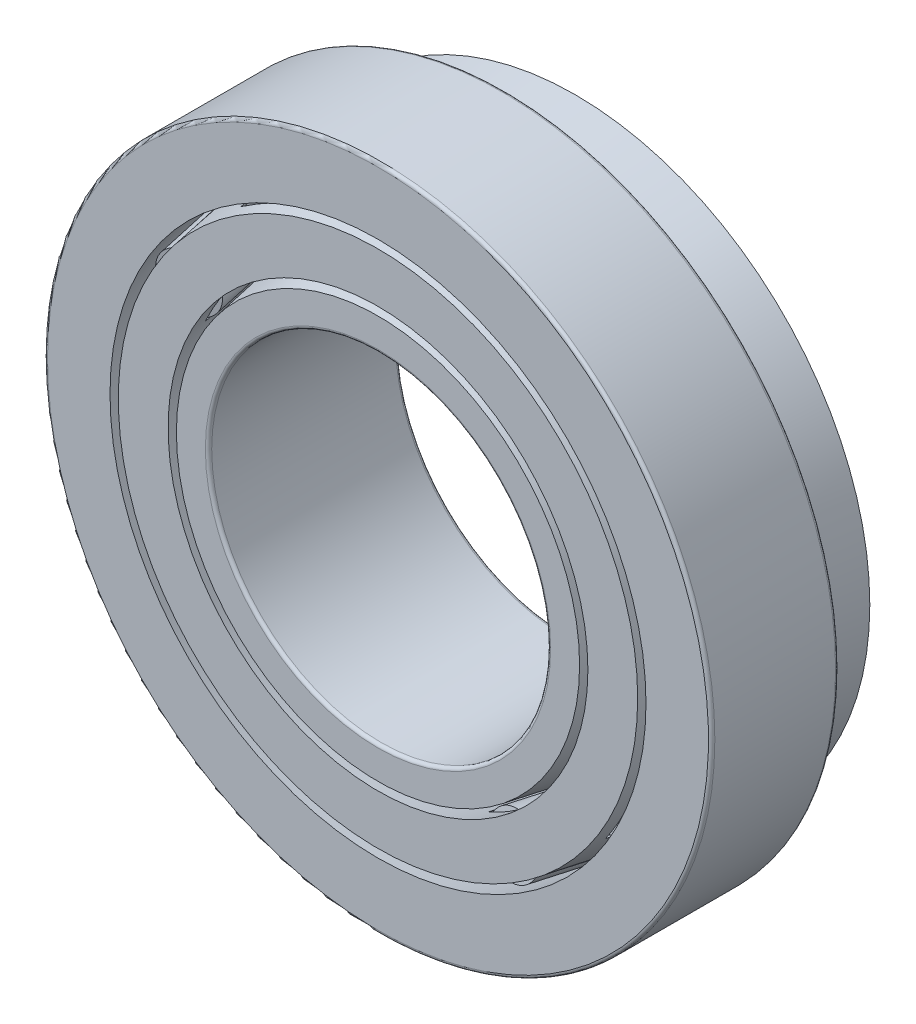
SolidWorks part; units mm, degrees
material "AISI 304"
ref_plane "Front Plane" through (0, 0, 0) normal (0, 0, 1) x (1, 0, 0)
ref_plane "Top Plane" through (0, 0, 0) normal (0, 1, 0) x (1, 0, 0)
ref_plane "Right Plane" through (0, 0, 0) normal (1, 0, 0) x (0, 0, -1)
sketch "Sketch1" plane through (0, 0, 0) normal (1, 0, 0) x (0, 0, -1)
  line L0 (-7.1298, 0) -> (7.1298, 0) construction
  line L1 (0, 0) -> (0, 25.0025) construction
  line L2 (-7.1298, 12.7) -> (7.1298, 12.7) construction
  line L3 (7.1298, 12.7) -> (7.1298, 17.621) construction
  line L4 (7.1298, 17.621) -> (-7.1298, 15.1067) construction
  line L5 (-7.1298, 15.1067) -> (-7.1298, 12.7) construction
  line L7 (-7.1298, 25.0025) -> (2.3952, 25.0025)
  line L8 (2.3952, 25.0025) -> (2.3952, 21.761)
  line L9 (2.3952, 21.761) -> (-7.1298, 20.0815)
  line L10 (-7.1298, 20.0815) -> (-7.1298, 25.0025)
  line L11 (-7.1298, 20.0815) -> (-6.279, 15.2567) construction
  line L12 (7.549, 22.6698) -> (8.3998, 17.8449) construction
  line L14 (-7.1298, 15.1067) -> (-6.279, 15.2567) construction
  line L15 (-7.1298, 15.1067) -> (8.3998, 17.8449) construction
  point P5 (0, 12.7)
  dimension "Width" = 14.2596
  dimension "OD" = 50.005
  dimension "Shaft Dia" = 25.4
  dimension "D1" = 100
  dimension "D2" = 12.3025
  dimension "D3" = 4.921
  dimension "Outer Wd" = 9.525
  dimension "Bearing Wd" = 15.5296
revolve "Revolve1" add sketch "Sketch1" angle 360 about L0
sketch "Sketch5" plane through (0, 0, 0) normal (1, 0, 0) x (0, 0, -1)
  line L0 (7.1298, 17.621) -> (-7.1298, 15.1067) construction
  line L1 (7.1298, 17.621) -> (-7.1298, 15.1067)
  line L2 (-7.1298, 15.1067) -> (-7.1298, 12.7)
  line L3 (-7.1298, 12.7) -> (7.1298, 12.7)
  line L4 (7.1298, 12.7) -> (7.1298, 17.621)
revolve "Revolve4" add sketch "Sketch5" angle 360 about L0
sketch "Sketch2" plane through (0, 0, 0) normal (1, 0, 0) x (0, 0, -1)
  line L0 (-7.1298, 19.4596) -> (-7.1298, 15.7285)
  line L1 (2.3952, 21.1392) -> (7.6554, 22.0667)
  line L2 (-7.1298, 15.7285) -> (2.3952, 17.408)
  line L3 (7.549, 22.6698) -> (8.3998, 17.8449) construction
  line L4 (2.3952, 17.408) -> (2.3952, 21.1392) construction
  line L5 (2.3952, 21.1392) -> (-7.1298, 19.4596)
  line L6 (2.3952, 21.761) -> (-7.1298, 20.0815) construction
  line L7 (7.1298, 17.621) -> (-7.1298, 15.1067) construction
  line L8 (-7.1298, 20.0815) -> (2.3952, 21.761) construction
  line L9 (-7.1298, 15.1067) -> (8.3998, 17.8449) construction
  line L10 (7.6554, 22.0667) -> (8.2934, 18.448)
  line L11 (-7.1298, 20.0815) -> (-7.1298, 19.4596) construction
  line L12 (-7.1298, 15.7285) -> (-7.1298, 15.1067) construction
  line L13 (2.3952, 25.0025) -> (2.3952, 21.761) construction
  line L14 (8.2934, 18.448) -> (2.3952, 17.408)
  dimension "D2" = 3.6744
  dimension "D1" = 4.8993
revolve "Revolve2" add sketch "Sketch2" angle 360 about L0
sketch "Sketch3" plane through (0, 0, 0) normal (1, 0, 0) x (0, 0, -1)
  line L0 (-7.1298, 17.5941) -> (2.3952, 19.2736) construction
  line L1 (-7.1298, 19.4596) -> (-7.1298, 15.7285) construction
  line L2 (2.3952, 17.408) -> (2.3952, 21.1392) construction
  line L3 (-5.8537, 17.8191) -> (-6.279, 20.2315)
  line L5 (-6.279, 20.2315) -> (1.9698, 21.686)
  line L6 (1.9698, 21.686) -> (2.3952, 19.2736)
  line L7 (2.3952, 19.2736) -> (-5.8537, 17.8191)
  line L8 (2.3952, 21.761) -> (-7.1298, 20.0815) construction
  line L9 (-7.1298, 17.5941) -> (-6.7044, 17.6691) construction
  line L10 (-7.1298, 20.0815) -> (-6.279, 15.2567) construction
  line L11 (-6.7044, 17.6691) -> (-6.279, 17.7441) construction
  line L12 (-6.279, 17.7441) -> (-5.8537, 17.8191) construction
revolve "Cut-Revolve1" cut sketch "Sketch3" angle 360 about L0
sketch "Sketch4" plane through (0, 0, 0) normal (1, 0, 0) x (0, 0, -1)
  line L0 (-6.2349, 19.9814) -> (2.014, 21.4359)
  line L1 (2.014, 21.4359) -> (2.3952, 19.2736)
  line L2 (2.3952, 19.2736) -> (-5.8537, 17.8191)
  line L3 (-7.1298, 17.5941) -> (-5.8537, 17.8191) construction
  line L4 (-5.8537, 17.8191) -> (-6.2349, 19.9814)
  line L6 (2.3952, 19.2736) -> (-5.8537, 17.8191) construction
  line L7 (2.3952, 21.761) -> (-7.1298, 20.0815) construction
  dimension "D1" = 0.254
revolve "Revolve3" add sketch "Sketch4" angle 360 about L0
ref_axis "Axis1" through (0, 0, -7.1298) along (0, 0, 1)
pattern_circular "CirPattern1" count 12 over 360 about axis through (0, 0, -7.1298) along (0, 0, 1) of "Cut-Revolve1"
pattern_circular "CirPattern2" count 12 over 360 about axis through (0, 0, -7.1298) along (0, 0, 1) of bodies 403
fillet "Fillet1" radius 0.2381 2 edges at (25.0025, 0, -2.3952) (25.0025, 0, 7.1298)
fillet "Fillet2" radius 0.2381 2 edges at (12.7, 0, -7.1298) (12.7, 0, 7.1298)
sketch "Sketch6" plane through (0, 0, 0) normal (1, 0, 0) x (0, 0, -1)
  line L0 (-42.0548, 25.0025) -> (-42.0548, 20.0815)
  line L1 (-42.0548, 20.0815) -> (-32.5298, 21.761)
  line L2 (-32.5298, 21.761) -> (-32.5298, 25.0025)
  line L3 (-32.5298, 25.0025) -> (-42.0548, 25.0025)
  line L4 (-7.1298, 25.0025) -> (2.3952, 25.0025) construction
  line L5 (-7.1298, 20.0815) -> (-7.1298, 25.0025) construction
  line L6 (2.3952, 25.0025) -> (2.3952, 21.761) construction
  dimension "Ring Separation" = 25.4
revolve "Revolve5" [suppressed] add sketch "Sketch6" angle 360 about L0
fillet "Fillet3" [suppressed] radius 0.2381
delete or keep bodies "Body-Delete1" [suppressed] type delete bodies bodies 399
sketch "Sketch8" plane through (0, 0, 0) normal (0, 0, 1) x (1, 0, 0)
  line L0 (0, 31.2531) -> (0, -31.2531) construction
  dimension "D1" = 62.5062
equation "\"D3@Sketch1\" = \"D2@Sketch1\"/2.5"
equation "\"D2@Sketch2\" = \"D1@Sketch2\"*.75"
equation "\"D1@Fillet1\" = \"Outer Wd@Sketch1\"*.025"
equation "\"D1@Fillet2\" = \"D1@Fillet1\""
equation "\"D1@Fillet3\" = \"D1@Fillet1\""
equation "\"Rollers@CirPattern2\" = \"D1@CirPattern1\""
equation "\"D1@Sketch8\" = \"OD@Sketch1\"*1.250"
